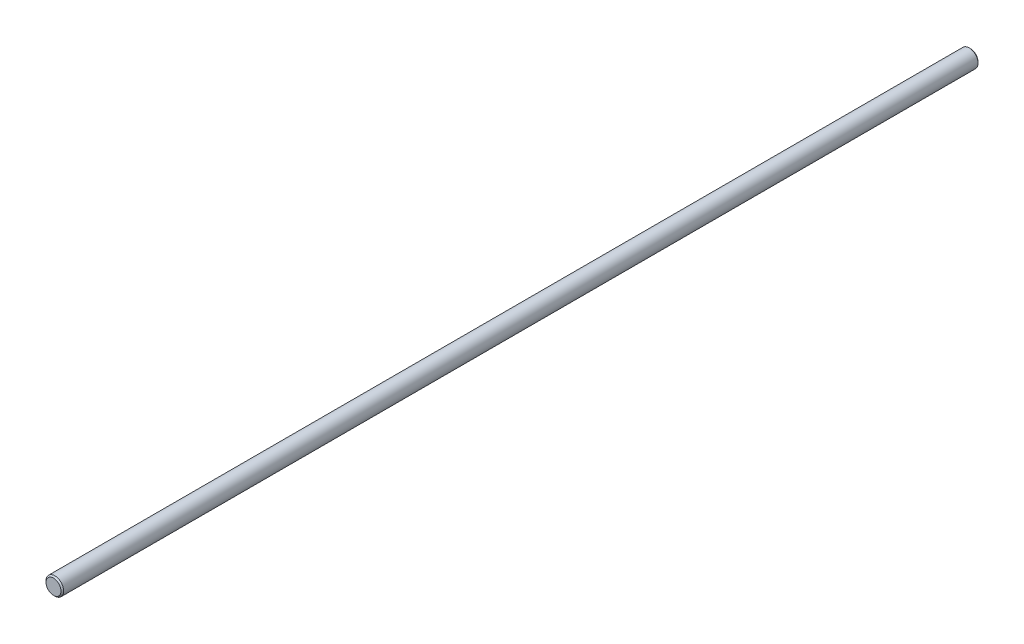
SolidWorks part; units mm, degrees
material "Cast Alloy Steel"
ref_plane "Front Plane" through (0, 0, 0) normal (0, 0, 1) x (1, 0, 0)
ref_plane "Top Plane" through (0, 0, 0) normal (0, 1, 0) x (1, 0, 0)
ref_plane "Right Plane" through (0, 0, 0) normal (1, 0, 0) x (0, 0, -1)
sketch "Sketch1" plane through (0, 0, 0) normal (1, 0, 0) x (0, 0, -1)
  line L0 (206.3115, 0) -> (-206.3115, 0) construction
  line L1 (-206.3115, -3.9688) -> (-206.3115, 3.9687) construction
  line L2 (-206.3115, 3.9687) -> (-207.7226, 3.9687) construction
  line L3 (206.3115, 3.9687) -> (206.3115, -3.9687) construction
  point P3 (206.3115, 3.9687)
  point P4 (0, 0)
  point P7 (-206.3115, 0)
  point P8 (-202.7837, -3.9688)
  point P12 (-194.4052, 3.9687)
  point P13 (206.3115, 0)
  point P15 (194.4052, 3.9688)
  point P19 (-190.9304, -3.9688)
  dimension "OD" = 7.9375
  dimension "Pitch" = 1.4111
  dimension "Length" = 412.623
  dimension "D1" = 3.5278
  dimension "D4" = 11.9062
  dimension "D5" = 11.9062
  dimension "SL" = 15.3811
sketch "Sketch2" plane through (0, 0, 0) normal (0, 0, 1) x (1, 0, 0)
  line L0 (0, -3.9688) -> (0, 3.9687) construction
  line L1 (-3.9687, 0) -> (3.9687, 0) construction
  circle A0 centre (0, 0) radius 3.9687
extrude "Boss-Extrude1" add sketch "Sketch2" along normal up to vertex (206.3115 mm away) and the other way up to vertex (206.3115 mm away) up to point (0, 0, 206.3115) other way up to point (0, 0, -206.3115)
chamfer "Chamfer1" distance 0.5953 angle 45 2 edges at (3.9687, 0, -206.3115) (3.9687, 0, 206.3115)
ref_axis "Center Axis 1" through (0, 0, -206.3115) along (0, 0, 1)
sketch "Sketch13" [suppressed] plane through (0, 0, 457.2) normal (0, 0, 1) x (1, 0, 0)
  circle A0 centre (0, 0) radius 3.9687
curve "Helix/Spiral1" [suppressed]
sketch "Sketch14" [suppressed] plane through (0, 0, 0) normal (1, 0, 0) x (0, 0, -1)
  line L0 (-458.5229, 4.1215) -> (-457.8174, 2.8994) construction
  line L1 (-457.8174, 2.8994) -> (-457.1118, 4.1215) construction
  line L2 (-457.1118, 4.1215) -> (-458.5229, 4.1215) construction
  line L3 (-457.8174, 4.1215) -> (-457.8174, 3.9687) construction
  line L4 (-457.8174, 3.9687) -> (-457.8174, 3.0522) construction
  line L5 (-457.8174, 3.0522) -> (-457.8174, 2.8994) construction
  line L6 (-458.4347, 3.9687) -> (-457.2, 3.9687) construction
  line L8 (-457.1559, 4.0451) -> (-458.4788, 4.0451) construction
  line L9 (-457.9056, 3.0522) -> (-457.7292, 3.0522)
  line L10 (-457.9056, 3.0522) -> (-457.7292, 3.0522) construction
  line L11 (-457.7292, 3.0522) -> (-457.1559, 4.0451)
  line L12 (-457.1559, 4.0451) -> (-458.4788, 4.0451)
  line L13 (-458.4788, 4.0451) -> (-457.9056, 3.0522)
  point P9 (-457.8174, 3.0522)
  point P14 (-457.8174, 3.9687)
  point P16 (-457.8174, 4.0451)
  point P17 (-457.8174, 4.0451)
  dimension "D1" = 1.4111
  dimension "D2" = 0.1764
sweep "Cut-Sweep1" [suppressed] cut profiles "Sketch14" path "Helix/Spiral1"
pattern_linear "LPattern1" [suppressed] count 10 spacing 15.3811 along (0, 0, -1) of bodies 503
ref_axis "Axis1" through (0, 0, 55.88) along (0, 0, -1)
equation "\"D1@Chamfer1\"=\"OD@Sketch1\"*.075"
equation "\"D4@Sketch1\"=\"OD@Sketch1\"*1.5"
equation "\"D5@Sketch1\"=\"OD@Sketch1\"*1.5"
equation "\"SL@Sketch1\"=\"Pitch@Sketch1\"*71-(5-0.45)"
equation "\"D4@Helix/Spiral1\"=\"Pitch@Sketch1\""
equation "\"D5@Helix/Spiral1\"= ( \"SL@Sketch1\" / \"Pitch@Sketch1\" ) + 1"
equation "\"D1@Sketch14\"=\"Pitch@Sketch1\""
equation "\"D2@Sketch14\"=\"D1@Sketch14\"/8"
equation "\"D3@LPattern1\"=\"SL@Sketch1\""
equation "\"D1@Sketch1\"=\"Pitch@Sketch1\"*2.5"
